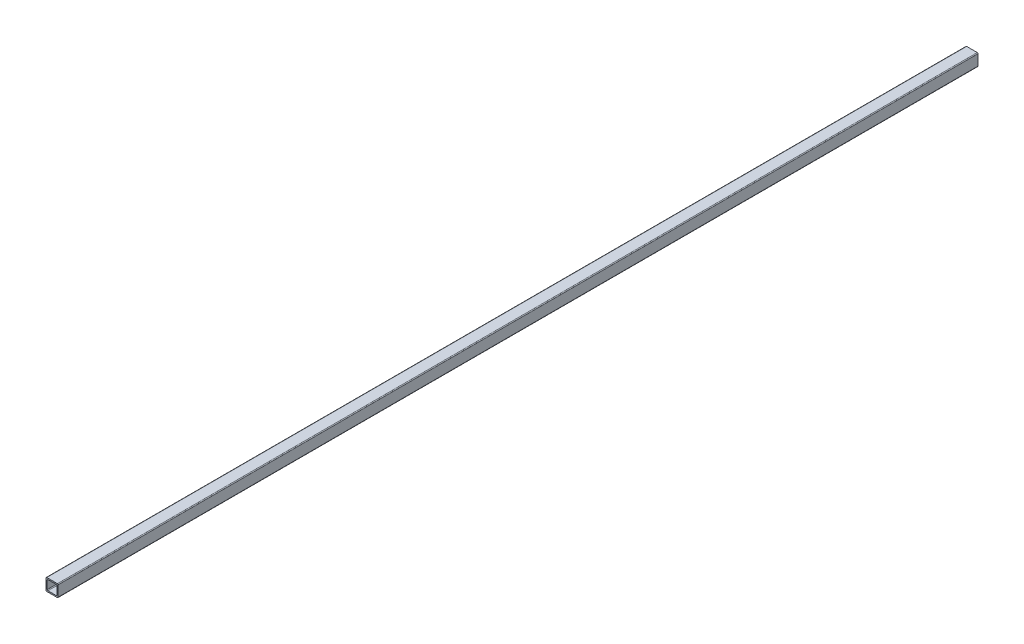
SolidWorks part; units mm, degrees
material "Hexcel AS4C (3000 Filaments)"
ref_plane "Front Plane" through (0, 0, 0) normal (0, 0, 1) x (1, 0, 0)
ref_plane "Top Plane" through (0, 0, 0) normal (0, 1, 0) x (1, 0, 0)
ref_plane "Right Plane" through (0, 0, 0) normal (1, 0, 0) x (0, 0, -1)
sketch "Sketch1" plane through (0, 0, 0) normal (0, 0, 1) x (1, 0, 0)
  line L1 (-3.95, 3.95) -> (3.95, 3.95)
  line L2 (-3.95, 3.95) -> (-3.95, -3.95)
  line L3 (-3.95, -3.95) -> (3.95, -3.95)
  line L4 (3.95, 3.95) -> (3.95, -3.95)
  line L5 (-3.95, 3.95) -> (3.95, -3.95) construction
  line L6 (-3.95, -3.95) -> (3.95, 3.95) construction
  line L7 (-3.15, 3.15) -> (3.15, 3.15)
  line L8 (-3.15, 3.15) -> (-3.15, -3.15)
  line L9 (-3.15, -3.15) -> (3.15, -3.15)
  line L10 (3.15, 3.15) -> (3.15, -3.15)
  line L11 (-3.15, 3.15) -> (3.15, -3.15) construction
  line L12 (-3.15, -3.15) -> (3.15, 3.15) construction
  point P0 (0, 0)
  point P6 (0, 0)
  dimension "D1" = 7.9
  dimension "D2" = 0.8
extrude "Boss-Extrude1" add sketch "Sketch1" along normal mid plane 600
fillet "Fillet1" radius 0.5 8 edges at (3.95, 3.95, 0) (3.15, 3.15, 0) (3.95, -3.95, 0) (3.15, -3.15, 0) (-3.95, -3.95, 0) (-3.15, -3.15, 0) (-3.15, 3.15, 0) (-3.95, 3.95, 0)
